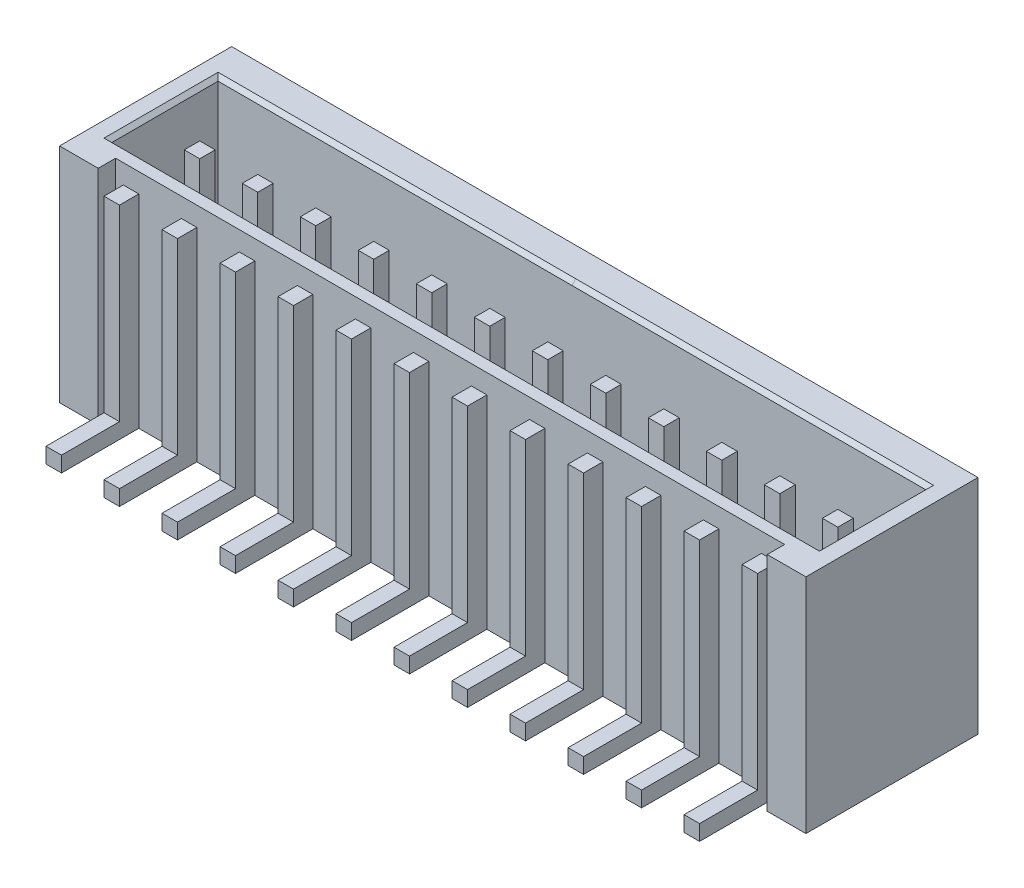
SolidWorks part; units mm, degrees
ref_plane "Front Plane" through (0, 0, 0) normal (0, 0, 1) x (1, 0, 0)
ref_plane "Top Plane" through (0, 0, 0) normal (0, 1, 0) x (1, 0, 0)
ref_plane "Right Plane" through (0, 0, 0) normal (1, 0, 0) x (0, 0, -1)
sketch "Sketch1" plane through (0, 0, 0) normal (0, 1, 0) x (1, 0, 0)
  line L0 (0, 0) -> (0, 4)
  line L1 (0, 4) -> (-9.65, 4)
  line L2 (-9.65, 4) -> (-9.65, -0.45)
  line L3 (-9.65, -0.45) -> (-8.65, -0.45)
  line L4 (-8.65, -0.45) -> (-8.65, 0)
  line L5 (-8.65, 0) -> (0, 0)
  dimension "D1" = 9.65
  dimension "D2" = 4.45
  dimension "D3" = 4
  dimension "D4" = 1
extrude "Boss-Extrude1" add sketch "Sketch1" along normal blind 5.75
sketch "Sketch2" plane through (0, 5.75, 0) normal (0, 1, 0) x (1, 0, 0)
  line L0 (0, 0) -> (0, 4) construction
  line L1 (0, 3.15) -> (-9.15, 3.15)
  line L2 (0, 3.15) -> (0, 0.4)
  line L3 (0, 0.4) -> (-9.15, 0.4)
  line L4 (-9.15, 3.15) -> (-9.15, 0.4)
  line L5 (0, 4) -> (-9.65, 4) construction
  dimension "D1" = 2.75
  dimension "D2" = 0.85
  dimension "D3" = 9.15
extrude "Cut-Extrude1" cut sketch "Sketch2" against normal blind 4
chamfer "Chamfer1" distance 0.1 angle 45 3 edges at (-4.575, 5.75, -0.4) (-9.15, 5.75, -1.775) (-4.575, 5.75, -3.15)
sketch "Sketch3" plane through (0, 1.75, 0) normal (0, 1, 0) x (1, 0, 0)
  line L0 (-9.15, 1.775) -> (-8.45, 1.775) construction
  line L1 (-8.45, 1.975) -> (-8.05, 1.975)
  line L2 (-8.45, 1.975) -> (-8.45, 1.575)
  line L3 (-8.45, 1.575) -> (-8.05, 1.575)
  line L4 (-8.05, 1.975) -> (-8.05, 1.575)
  line L5 (-9.15, 3.15) -> (-9.15, 0.4) construction
  line L6 (0, 0.4) -> (0, 3.15) construction
  point P8 (-8.25, 1.975)
  dimension "D1" = 8.25
  dimension "D2" = 0.4
extrude "Boss-Extrude2" add sketch "Sketch3" along normal blind 3.5
sketch "Sketch4" plane through (0, 0, 0) normal (0, 0, 1) x (1, 0, 0)
  line L0 (-8.65, 0) -> (0, 0) construction
  line L1 (-8.05, 1.75) -> (-8.45, 1.75)
  line L2 (-8.05, 1.75) -> (-8.05, 0)
  line L3 (-8.05, 0) -> (-8.45, 0)
  line L4 (-8.45, 1.75) -> (-8.05, 1.75)
  line L5 (-8.05, 1.75) -> (-8.05, 5.25)
  line L6 (-8.05, 5.25) -> (-8.45, 5.25)
  line L7 (-8.45, 5.25) -> (-8.45, 1.75)
  line L8 (-8.45, 1.75) -> (-8.05, 1.75)
  line L9 (-8.05, 1.75) -> (-8.05, 5.25)
  line L10 (-8.05, 5.25) -> (-8.45, 5.25)
  line L11 (-8.45, 5.25) -> (-8.45, 1.75)
  line L12 (-8.45, 1.75) -> (-8.45, 0)
  point P9 (0, 0)
  line M9 (-8.65, 0) -> (0, 0)
  dimension "D1" = 0
extrude "Boss-Extrude3" add sketch "Sketch4" along normal blind 0.5 contours L10 L11 L1 L9 | L1 L12 L2 M9 region at (-8.25, 0.875, 0) region at (-8.25, 3.5, 0)
sketch "Sketch5" plane through (0, 0, 0.5) normal (0, 0, 1) x (1, 0, 0)
  line L0 (-8.05, 0) -> (-8.05, 5.25) construction
  line L1 (-8.45, 0) -> (-8.05, 0)
  line L2 (-8.45, 0) -> (-8.45, 0.4)
  line L3 (-8.45, 0.4) -> (-8.05, 0.4)
  line L4 (-8.05, 0) -> (-8.05, 0.4)
  dimension "D1" = 0.4
extrude "Boss-Extrude4" add sketch "Sketch5" along normal blind 1.5
pattern_linear "LPattern1" count 6 spacing 1.5 along (1, 0, 0) of "Boss-Extrude2", "Boss-Extrude3", "Boss-Extrude4"
mirror "Mirror1" about plane through (0, 5.75, 0) normal (-1, 0, 0) of "Chamfer1", "Cut-Extrude1", "Boss-Extrude1", "LPattern1"
